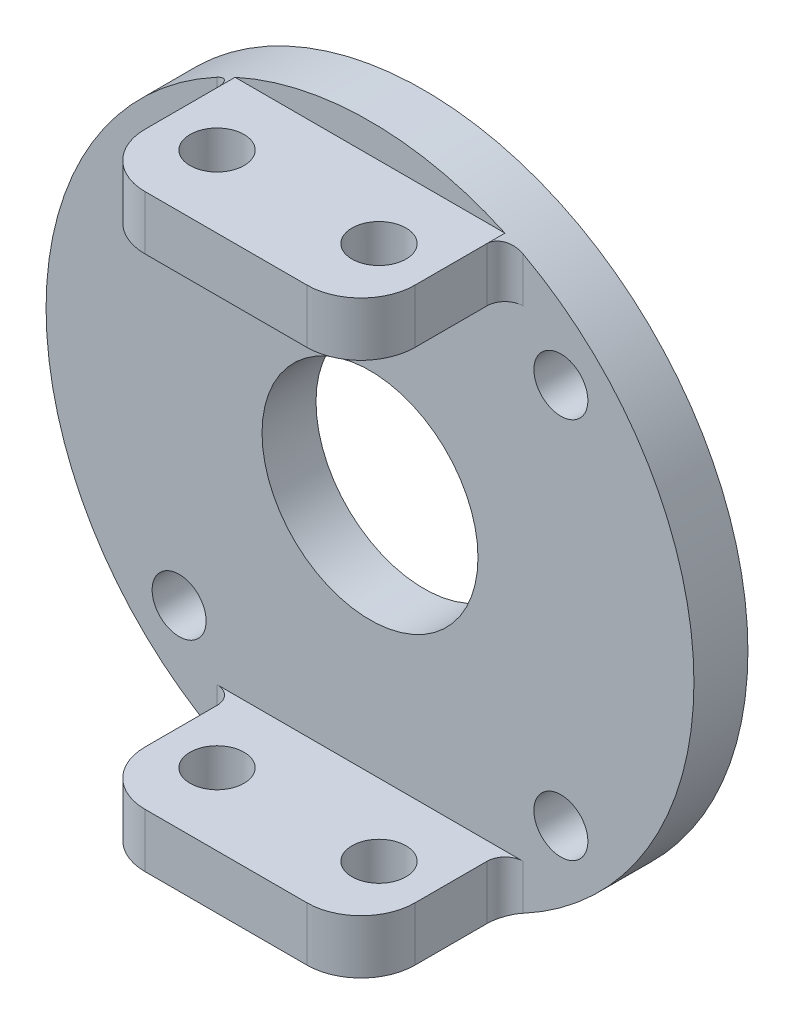
SolidWorks part; units mm, degrees
ref_plane "Спереди" through (0, 0, 0) normal (0, 0, 1) x (1, 0, 0)
ref_plane "Сверху" through (0, 0, 0) normal (0, 1, 0) x (1, 0, 0)
ref_plane "Справа" through (0, 0, 0) normal (1, 0, 0) x (0, 0, -1)
sketch "Эскиз1" plane through (0, 0, 0) normal (0, 0, 1) x (1, 0, 0)
  circle A0 centre (0, 0) radius 18
  dimension "D1" = 36
extrude "Бобышка-Вытянуть1" add sketch "Эскиз1" along normal blind 3
sketch "Эскиз2" plane through (0, 0, 3) normal (0, 0, 1) x (1, 0, 0)
  line L0 (0, 0) -> (-32.0715, 0) construction
  line L1 (0, 0) -> (-18.7433, 18.7433) construction
  circle A0 centre (0, 0) radius 15 construction
  circle A1 centre (-10.6066, 10.6066) radius 1.5
  circle A2 centre (10.6066, 10.6066) radius 1.5
  circle A3 centre (10.6066, -10.6066) radius 1.5
  circle A4 centre (-10.6066, -10.6066) radius 1.5
  point P5 (-10.6066, 10.6066)
  point P14 (0, 0)
  dimension "D1" = 30
  dimension "D2" = 3
  dimension "D4" = 45
  dimension "D3" = 4
extrude "Вырез-Вытянуть1" cut sketch "Эскиз2" against normal blind 3 contours A4 | A3 | A2 | A1 region at (10.6066, 10.6066, 3) region at (10.6066, -10.6066, 3) region at (-10.6066, -10.6066, 3)
sketch "Эскиз4" plane through (0, 0, 3) normal (0, 0, 1) x (1, 0, 0)
  line L0 (0, 0) -> (9.6672, 0) construction
  line L1 (7.5, 16.3631) -> (-7.5, 16.3631)
  line L2 (7.5, 16.3631) -> (7.5, 13.3631)
  line L3 (7.5, 13.3631) -> (-7.5, 13.3631)
  line L4 (-7.5, 16.3631) -> (-7.5, 13.3631)
  line L5 (7.5, 16.3631) -> (-7.5, 13.3631) construction
  line L6 (7.5, 13.3631) -> (-7.5, 16.3631) construction
  line L7 (7.5, -13.3631) -> (-7.5, -13.3631)
  line L8 (-7.5, -16.3631) -> (-7.5, -13.3631)
  line L9 (7.5, -16.3631) -> (-7.5, -16.3631)
  line L10 (7.5, -16.3631) -> (7.5, -13.3631)
  circle A0 centre (0, 0) radius 18 construction
  point P0 (0, 14.8631)
  dimension "D1" = 3
  dimension "D2" = 15
extrude "Бобышка-Вытянуть2" add sketch "Эскиз4" along normal blind 8
sketch "Эскиз5" plane through (0, 16.3631, 0) normal (0, 1, 0) x (1, 0, 0)
  line L0 (0, 0) -> (0, -15.2478) construction
  line L1 (18, 0) -> (-18, 0) construction
  line L2 (7.5, -3) -> (-7.5, -3) construction
  circle A0 centre (-4.5, -7) radius 1.5
  circle A1 centre (4.5, -7) radius 1.5
  dimension "D1" = 3
  dimension "D2" = 9
  dimension "D3" = 4
extrude "Вырез-Вытянуть2" cut sketch "Эскиз5" against normal blind 37
fillet "Скругление1" radius 3 4 edges at (-7.5, -14.8631, 11) (7.5, -14.8631, 11) (7.5, 14.8631, 11) (-7.5, 14.8631, 11)
fillet "Скругление2" radius 1 4 edges at (7.5, 14.8631, 3) (7.5, -14.8631, 3) (-7.5, -14.8631, 3) (-7.5, 14.8631, 3)
sketch "Эскиз6" plane through (0, 0, 3) normal (0, 0, 1) x (1, 0, 0)
  circle A0 centre (0, 0) radius 6
  dimension "D1" = 12
extrude "Вырез-Вытянуть3" cut sketch "Эскиз6" against normal blind 37
